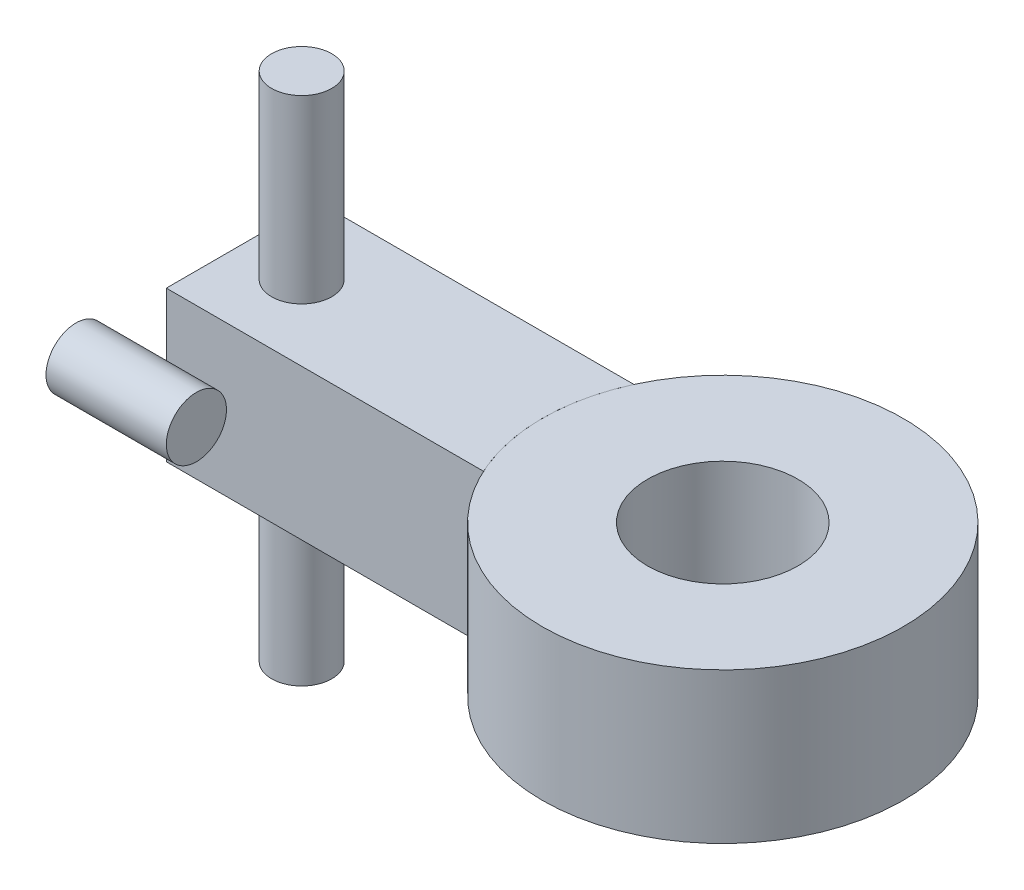
SolidWorks part; units mm, degrees
ref_plane "Front Plane" through (0, 0, 0) normal (0, 0, 1) x (1, 0, 0)
ref_plane "Top Plane" through (0, 0, 0) normal (0, 1, 0) x (1, 0, 0)
ref_plane "Right Plane" through (0, 0, 0) normal (1, 0, 0) x (0, 0, -1)
sketch "Sketch1" plane through (0, 0, 0) normal (0, 1, 0) x (1, 0, 0)
  circle A0 centre (0, 0) radius 12.5
  circle A1 centre (0, 0) radius 30
  dimension "D1" = 25
extrude "Boss-Extrude1" add sketch "Sketch1" along normal blind 25
ref_plane "Plane1" through (-30, 0, 0) normal (-1, 0, 0) x (0, 0, 1)
sketch "Sketch3" plane through (-30, 0, 0) normal (-1, 0, 0) x (0, 0, 1)
  line L0 (-12.5, 0) -> (12.5, 0) construction
  line L1 (-12.5, -25) -> (12.5, -25)
  line L2 (-12.5, 0) -> (-12.5, 25)
  line L3 (-12.5, 25) -> (12.5, 25)
  line L4 (12.5, 0) -> (12.5, 25)
  line L5 (0, 0) -> (12.5, 25) construction
  line L6 (-12.5, 25) -> (0, 0) construction
  line L7 (-12.5, 0) -> (12.5, 0)
  point P0 (0, 0)
extrude "Boss-Extrude2" add sketch "Sketch3" along normal blind 50 and the other way up to surface separate body contours L2 L7 L4 L3 region at (-30, 12.5, 0) other way up to face at (0, 25, 30)
sketch "Sketch4" plane through (0, 0, 0) normal (0, -1, 0) x (1, 0, 0)
  circle A0 centre (-70, 0) radius 5
extrude "Boss-Extrude3" add sketch "Sketch4" along normal blind 30 and the other way blind 55
sketch "Sketch5" plane through (-80, 0, 0) normal (-1, 0, 0) x (0, 0, 1)
  circle A2 centre (17.5, 12.5) radius 5
extrude "Boss-Extrude4" add sketch "Sketch5" along normal blind 10 and the other way blind 10 separate body
